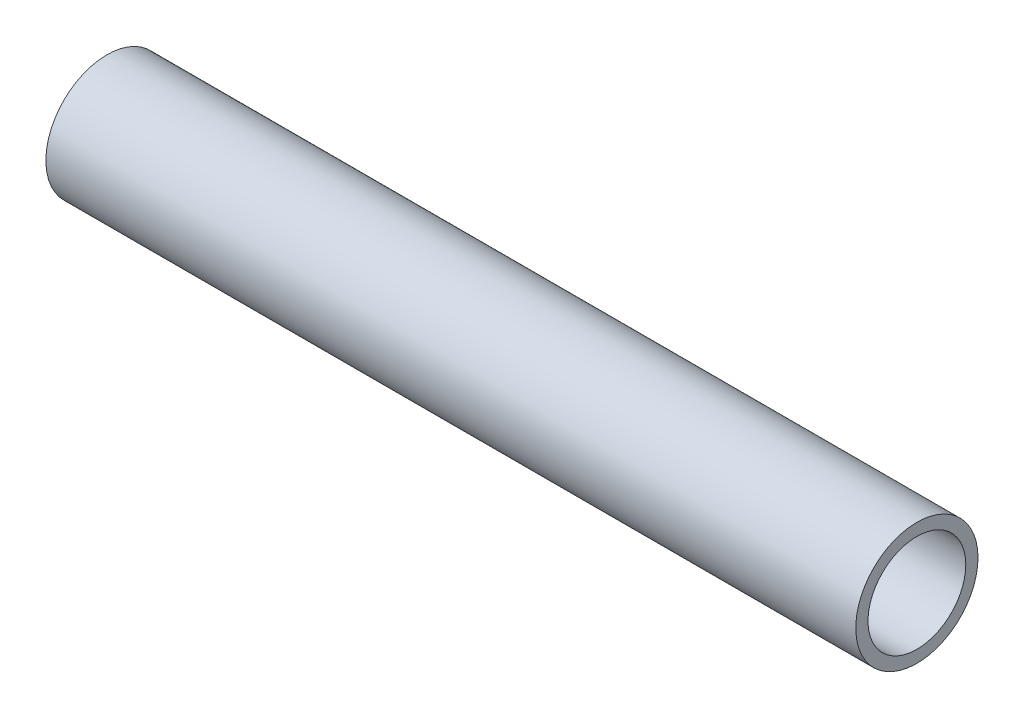
SolidWorks part; units mm, degrees
material "PC High Viscosity"
ref_plane "Front Plane" through (0, 0, 0) normal (0, 0, 1) x (1, 0, 0)
ref_plane "Top Plane" through (0, 0, 0) normal (0, 1, 0) x (1, 0, 0)
ref_plane "Right Plane" through (0, 0, 0) normal (1, 0, 0) x (0, 0, -1)
sketch "Sketch1" plane through (0, 0, 0) normal (1, 0, 0) x (0, 0, -1)
  circle A0 centre (0, 0) radius 15.875
  dimension "D1" = 31.75
extrude "Extrude-Thin1" add sketch "Sketch1" along normal mid plane 210.349 thin thin type one direction reverse wall 3.175
